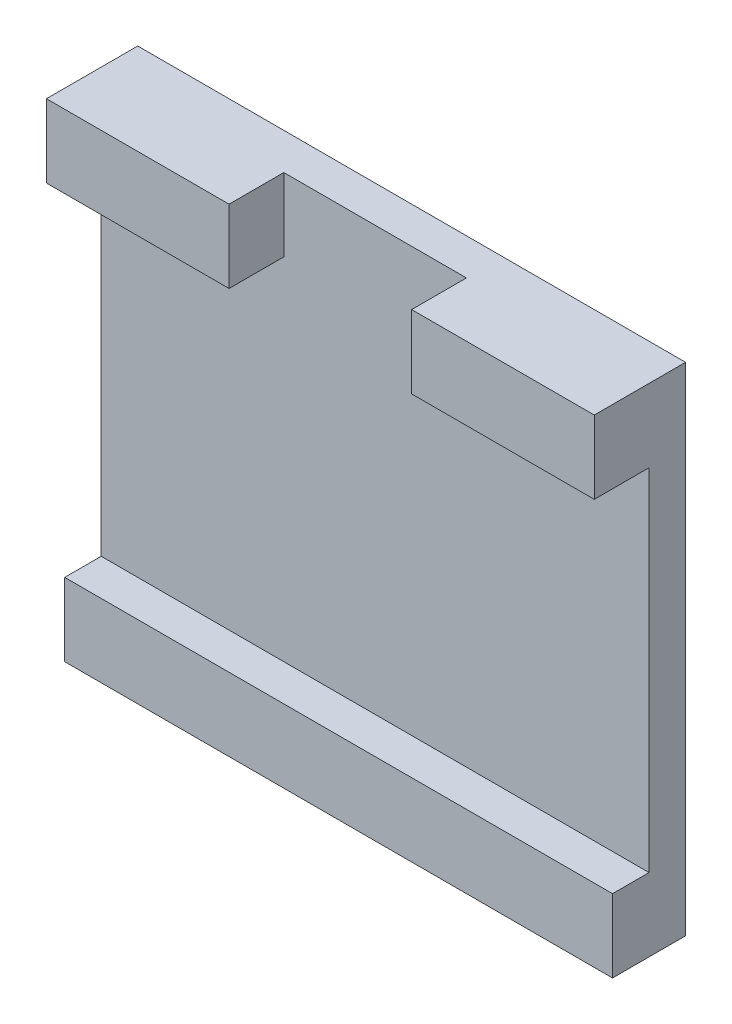
SolidWorks part; units mm, degrees
ref_plane "Front Plane" through (0, 0, 0) normal (0, 0, 1) x (1, 0, 0)
ref_plane "Top Plane" through (0, 0, 0) normal (0, 1, 0) x (1, 0, 0)
ref_plane "Right Plane" through (0, 0, 0) normal (1, 0, 0) x (0, 0, -1)
sketch "Sketch1" plane through (0, 0, 0) normal (0, 0, 1) x (1, 0, 0)
  line L1 (-15, 0) -> (15, 0)
  line L2 (-15, 0) -> (-15, 27.2)
  line L3 (-15, 27.2) -> (15, 27.2)
  line L4 (15, 0) -> (15, 27.2)
  line L5 (-15, 27.2) -> (15, 27.2)
  line L6 (-15, 27.2) -> (-15, 23.2)
  line L7 (-15, 23.2) -> (15, 23.2)
  line L8 (15, 27.2) -> (15, 23.2)
  line L9 (15, 0) -> (-15, 0)
  line L10 (15, 0) -> (15, 4)
  line L11 (15, 4) -> (-15, 4)
  line L12 (-15, 0) -> (-15, 4)
  point P4 (0, 0)
  dimension "D1" = 19.2
  dimension "D2" = 30
  dimension "D3" = 4
  dimension "D4" = 4
extrude "Boss-Extrude1" add sketch "Sketch1" against normal blind 2 contours L2 L7 L4 L3 | L11 L4 L7 L2 | L4 L11 L2 L1 region at (0, 2, 0) region at (0, 13.6, 0) region at (0, 25.2, 0)
extrude "Boss-Extrude2" add sketch "Sketch1<4>" along normal blind 2 contours L4 L11 L2 L1 region at (0, 2, 0)
sketch "Sketch1<4>" plane through (0, 0, 0) normal (0, 0, 1) x (1, 0, 0) same geometry as "Sketch1"
extrude "Boss-Extrude3" add sketch "Sketch1<5>" along normal blind 3 contours L2 L7 L4 L3 region at (0, 25.2, 0)
sketch "Sketch1<5>" plane through (0, 0, 0) normal (0, 0, 1) x (1, 0, 0) same geometry as "Sketch1"
ref_plane "enclosure" through (0, 2, 0) normal (0, 1, 0) x (1, 0, 0)
sketch "Sketch3" plane through (0, 23.2, 0) normal (0, -1, 0) x (1, 0, 0)
  line L0 (-15, 3) -> (15, 3) construction
  line L1 (-5, 0) -> (5, 0)
  line L2 (-5, 0) -> (-5, 3)
  line L3 (-5, 3) -> (5, 3)
  line L4 (5, 0) -> (5, 3)
  line L5 (-5, 0) -> (5, 3) construction
  line L6 (-5, 3) -> (5, 0) construction
  line L7 (-15, 0) -> (15, 0) construction
  line L8 (0, 1.5) -> (0, 0) construction
  point P0 (0, 1.5)
  dimension "D1" = 10
extrude "Cut-Extrude1" cut sketch "Sketch3" against normal up to next
